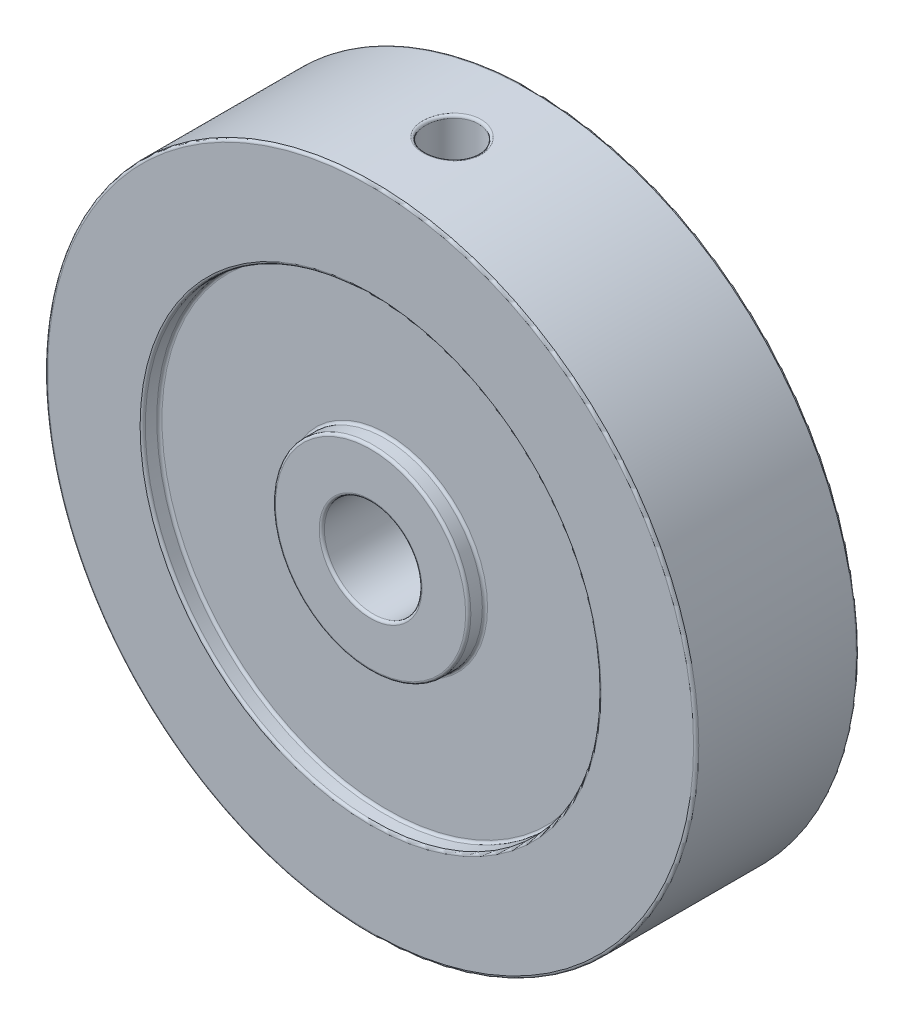
SolidWorks part; units mm, degrees
material "Alloy Steel"
ref_plane "Front Plane" through (0, 0, 0) normal (0, 0, 1) x (1, 0, 0)
ref_plane "Top Plane" through (0, 0, 0) normal (0, 1, 0) x (1, 0, 0)
ref_plane "Right Plane" through (0, 0, 0) normal (1, 0, 0) x (0, 0, -1)
sketch "Sketch1" plane through (0, 0, 0) normal (0, 0, 1) x (1, 0, 0)
  circle A0 centre (0, 0) radius 15.875
  dimension "D1" = 31.75
extrude "Boss-Extrude1" add sketch "Sketch1" along normal mid plane 7.9375
sketch "Sketch2" plane through (0, 0, 3.9688) normal (0, 0, 1) x (1, 0, 0)
  circle A0 centre (0, 0) radius 2.3813
  circle A1 centre (0, 0) radius 11.1125
  circle A2 centre (0, 0) radius 4.7625
  dimension "D1" = 4.7625
  dimension "D2" = 22.225
  dimension "D3" = 22.225
  dimension "D4" = 9.525
extrude "Cut-Extrude1" cut sketch "Sketch2" against normal through all contours A0 region at (0, 0, 3.9688)
extrude "Cut-Extrude2" cut sketch "Sketch2<3>" against normal blind 0.8128 contours A1 A2 region at (-10.7982, 0, 3.9688)
sketch "Sketch2<3>" plane through (0, 0, 3.9688) normal (0, 0, 1) x (1, 0, 0) same geometry as "Sketch2"
mirror "Mirror1" about plane through (0, 0, 0) normal (0, 0, 1) of "Cut-Extrude2"
ref_plane "Plane1" through (0, 15.875, 0) normal (0, 1, 0) x (1, 0, 0)
hole_wizard "#5-40 Tapped Hole1" positions "Sketch3" profile "Sketch4" tap size "#5-40" standard "ANSI Inch"
sketch "Sketch3" plane through (0, 15.875, 0) normal (0, 1, 0) x (1, 0, 0)
  point P0 (0, 0)
sketch "Sketch4" plane through (0, 15.875, 0) normal (1, 0, 0) x (0, 0, 1)
  line L0 (0, 0) -> (0, 17.1575)
  line L1 (0, 17.1575) -> (1.289, 16.383)
  line L2 (1.289, 16.383) -> (1.289, 0)
  line L5 (1.289, 0) -> (0, 0)
  line L10 (0, 17.1575) -> (-1.2891, 16.383) construction
  line L11 (0, -6.35) -> (0, 107.95) construction
  dimension "Tap Drill Dia." = 2.5781
  dimension "Tap Drill Depth" = 16.383
  dimension "Drill Angle" = 118
cosmetic thread "Hole Thread1" parameters "D1"=6.35, "D2"=3.175
fillet "Fillet1" radius 0.127 13 edges at (11.1125, 0, -3.9688) (4.7625, 0, -3.9688) (2.3813, 0, -3.9688) (11.1125, 0, -3.156) (4.7625, 0, -3.156) (4.7625, 0, 3.9688) (2.3813, 0, 3.9688) (11.1125, 0, 3.156) (4.7625, 0, 3.156) (11.1125, 0, 3.9688) (15.875, 0, -3.9688) (15.875, 0, 3.9688) (0.2917, 15.8723, -1.2556)
